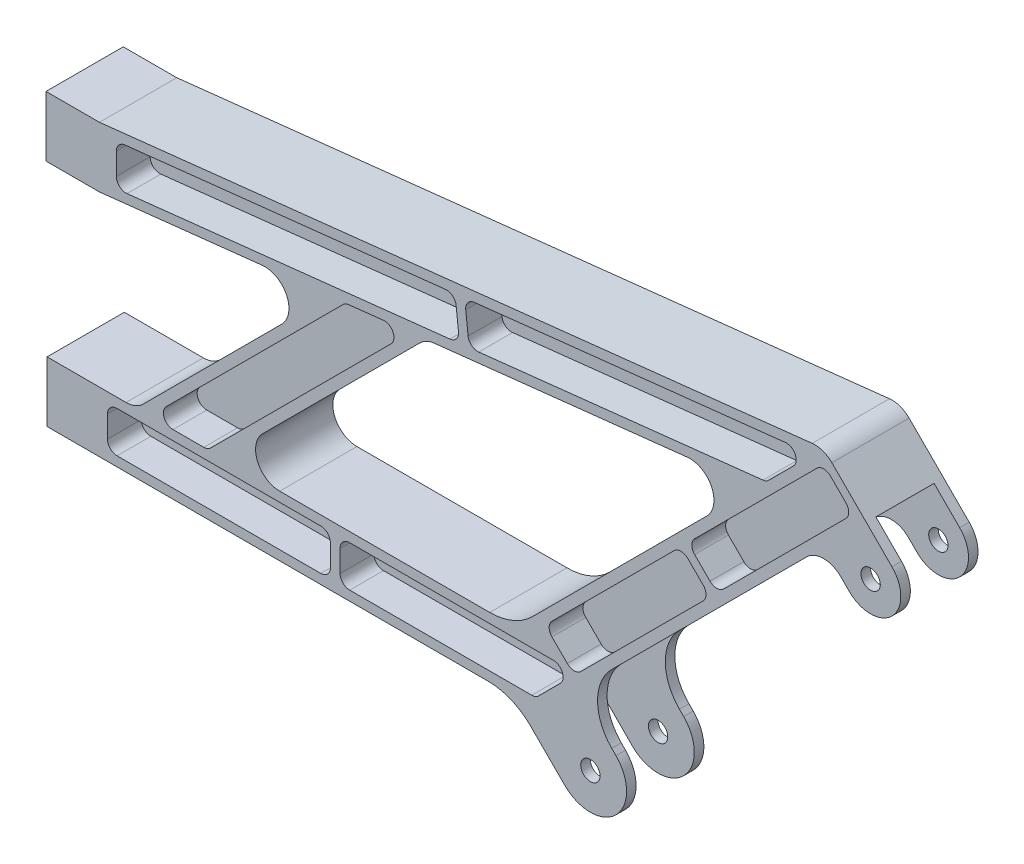
SolidWorks part; units mm, degrees
material "6061-T6 (SS)"
ref_plane "Front Plane" through (0, 0, 0) normal (0, 0, 1) x (1, 0, 0)
ref_plane "Top Plane" through (0, 0, 0) normal (0, 1, 0) x (1, 0, 0)
ref_plane "Right Plane" through (0, 0, 0) normal (1, 0, 0) x (0, 0, -1)
sketch "Sketch1" plane through (0, 0, 0) normal (0, 0, 1) x (1, 0, 0)
  line L1 (-157.7639, -90.8401) -> (-244.7728, -90.8401)
  line L2 (-67.8181, -11.2496) -> (-140.0863, -83.5177)
  line L3 (-16.0497, 33.7315) -> (8.8396, 8.8381)
  line L4 (-12.3744, -5.3033) -> (-8.8388, -8.8388)
  line L5 (-26.5165, -5.3033) -> (-107.2487, -86.0355)
  line L6 (-140.8326, -123.1624) -> (-126.6942, -137.3008)
  line L7 (-158.5102, -115.8401) -> (-341.1373, -115.8401)
  line L8 (-341.1373, -115.8401) -> (-341.1373, -90.8401)
  line L9 (-308.4124, -90.8401) -> (-341.1373, -90.8401)
  line L11 (-341.5776, -20.8403) -> (-319.4176, -20.8403)
  line L12 (-341.5776, -20.8403) -> (-341.5776, 4.1597)
  line L13 (-341.5776, 4.1597) -> (-319.4176, 4.1597)
  line L14 (-107.2487, -114.3198) -> (-105.481, -116.0876)
  line L15 (-319.4176, 4.1597) -> (-24.2138, 36.6012)
  line L17 (-301.3413, -87.9111) -> (-243.8773, -30.4471)
  line L18 (-75.9816, 5.7616) -> (-180.7131, -5.7479)
  line L19 (-251.8438, -73.769) -> (-186.6918, -8.6169)
  line L20 (-252.0407, -13.4359) -> (-319.4176, -20.8403)
  arc A4 (8.8388, -8.8388) -> (8.8396, 8.8381) centre (0, 0) ccw
  arc A5 (-8.8388, -8.8388) -> (8.8388, -8.8388) centre (0, 0) ccw
  arc A6 (-12.3744, -5.3033) -> (-26.5165, -5.3033) centre (-19.4454, -12.3744) ccw
  arc A7 (-107.2487, -86.0355) -> (-107.2487, -114.3198) centre (-93.1066, -100.1777) ccw
  arc A8 (-105.481, -137.3008) -> (-105.481, -116.0876) centre (-116.0876, -126.6942) ccw
  arc A9 (-126.6942, -137.3008) -> (-105.481, -137.3008) centre (-116.0876, -126.6942) ccw
  circle A12 centre (-116.0876, -126.6942) radius 4
  circle A13 centre (0, 0) radius 4
  arc A15 (-158.5102, -115.8401) -> (-140.8326, -123.1624) centre (-158.5102, -140.8401) cw
  arc A16 (-157.7639, -90.8401) -> (-140.0863, -83.5177) centre (-157.7639, -65.8401) ccw
  arc A20 (-67.8181, -11.2496) -> (-75.9816, 5.7616) centre (-74.8892, -4.1785) ccw
  arc A21 (-16.0497, 33.7315) -> (-24.2138, 36.6012) centre (-23.1214, 26.661) ccw
  arc A22 (-186.6918, -8.6169) -> (-180.7131, -5.7479) centre (-179.6207, -15.688) cw
  arc A23 (-244.7728, -90.8401) -> (-251.8438, -73.769) centre (-244.7728, -80.8401) cw
  arc A25 (-308.4124, -90.8401) -> (-301.3413, -87.9111) centre (-308.4124, -80.8401) ccw
  arc A26 (-252.0407, -13.4359) -> (-243.8773, -30.4471) centre (-250.9484, -23.3761) cw
  point P38 (0, 0)
  point P50 (-318.5667, -20.8403)
  dimension "D2" = 25
  dimension "D3" = 25
  dimension "D7" = 10
  dimension "D9" = 22.16
  dimension "D6" = 25
  dimension "D1" = 25
  dimension "D4" = 25
  dimension "D5" = 25
  dimension "D8" = 119.9998
extrude "Boss-Extrude1" add sketch "Sketch1" along normal blind 32
sketch "Sketch2" plane through (0, 0, 32) normal (0, 0, 1) x (1, 0, 0)
  line L0 (-107.2487, -86.0355) -> (-26.5165, -5.3033) construction
  line L1 (-137.5386, -110.6685) -> (-128.5386, -101.6685)
  line L2 (-131.367, -94.8401) -> (-215.77, -94.8401)
  line L3 (-67.8181, -11.2496) -> (-140.0863, -83.5177) construction
  line L4 (-107.2487, -86.0355) -> (-26.5165, -5.3033)
  line L5 (-67.8181, -11.2496) -> (-140.0863, -83.5177)
  line L6 (-22.272, 28.6397) -> (-72.893, -21.9813)
  line L7 (-119.9767, -93.1066) -> (-69.3575, -42.4874)
  line L8 (-131.9975, -86.7426) -> (-125.6335, -93.1066)
  line L9 (-10.2515, 22.275) -> (-16.6149, 28.6394)
  line L10 (-64.9897, -14.078) -> (-137.2579, -86.3462) construction
  line L11 (-110.0772, -83.2071) -> (-29.3449, -2.4749) construction
  line L12 (-341.1373, -115.8401) -> (-158.5102, -115.8401) construction
  line L13 (-341.1373, -115.8401) -> (-158.5102, -115.8401)
  line L14 (-312.1373, -111.8401) -> (-227.77, -111.8401)
  line L15 (-341.1373, -111.8401) -> (-158.5102, -111.8401) construction
  line L16 (-341.1373, -90.8401) -> (-341.1373, -115.8401) construction
  line L17 (-316.1373, -98.8401) -> (-316.1373, -107.8401)
  line L18 (-157.7639, -90.8401) -> (-244.7728, -90.8401) construction
  line L19 (8.8396, 8.8381) -> (-16.0497, 33.7315) construction
  line L20 (-140.8326, -123.1624) -> (-126.6942, -137.3008) construction
  line L21 (-65.1149, -38.2448) -> (-77.1357, -26.224) construction
  line L22 (-72.893, -27.6382) -> (-66.5291, -34.0022)
  line L23 (-75.7215, -30.4666) -> (-69.3575, -36.8306)
  line L24 (-81.3783, -30.4666) -> (-131.9975, -81.0858)
  line L25 (-60.8722, -34.0022) -> (-10.2517, 16.6183)
  line L26 (-221.77, -94.8401) -> (-221.77, -111.8401) construction
  line L27 (-219.77, -98.8401) -> (-219.77, -107.8401)
  line L28 (-223.77, -98.8401) -> (-223.77, -107.8401)
  line L29 (-215.77, -111.8401) -> (-140.367, -111.8401)
  line L30 (-227.77, -94.8401) -> (-312.1373, -94.8401)
  line L38 (-308.8907, 1.2925) -> (-176.1091, 15.8845)
  line L39 (-24.2138, 36.6012) -> (-319.4176, 4.1597) construction
  line L40 (-308.0168, -15.7138) -> (-174.2521, -1.0137)
  line L41 (-75.9816, 5.7616) -> (-180.7131, -5.7479) construction
  line L42 (-312.4538, -2.6836) -> (-312.4538, -11.7378)
  line L43 (-32.0118, 24.5568) -> (-42.1838, 14.3847)
  line L44 (-170.145, 16.5399) -> (-168.288, -0.3583) construction
  line L45 (-171.6961, 12.3454) -> (-170.713, 3.3993)
  line L46 (-167.7201, 12.7824) -> (-166.7369, 3.8362)
  line L47 (-164.181, 17.1954) -> (-35.2771, 31.3613)
  line L48 (-162.3239, 0.2971) -> (-44.5753, 13.2371)
  line L49 (-218.5658, -10.7925) -> (-291.7849, -84.0116)
  line L50 (-243.8773, -30.4471) -> (-301.3413, -87.9111) construction
  line L51 (-198.6096, -14.8779) -> (-273.4002, -89.6685)
  line L52 (-186.6918, -8.6169) -> (-251.8438, -73.769) construction
  line L53 (-216.1743, -9.6449) -> (-201.875, -8.0734)
  line L54 (-288.9565, -90.8401) -> (-276.2286, -90.8401)
  line L55 (-341.5776, 4.1597) -> (-341.5776, -20.8403) construction
  arc A0 (-22.272, 28.6397) -> (-16.6149, 28.6394) centre (-19.4436, 25.8113) cw
  arc A1 (-10.2517, 16.6183) -> (-10.2515, 22.275) centre (-13.0801, 19.4468) ccw
  arc A2 (-119.9767, -93.1066) -> (-125.6335, -93.1066) centre (-122.8051, -90.2782) cw
  arc A3 (-131.9975, -81.0858) -> (-131.9975, -86.7426) centre (-129.169, -83.9142) ccw
  arc A4 (-312.1373, -111.8401) -> (-316.1373, -107.8401) centre (-312.1373, -107.8401) cw
  arc A5 (-312.1373, -94.8401) -> (-316.1373, -98.8401) centre (-312.1373, -98.8401) ccw
  arc A6 (-140.367, -111.8401) -> (-137.5386, -110.6685) centre (-140.367, -107.8401) ccw
  arc A7 (-128.5386, -101.6685) -> (-131.367, -94.8401) centre (-131.367, -98.8401) ccw
  arc A8 (-75.7215, -30.4666) -> (-81.3783, -30.4666) centre (-78.5499, -33.295) ccw
  arc A9 (-69.3575, -36.8306) -> (-69.3575, -42.4874) centre (-72.1859, -39.659) cw
  arc A10 (-66.5291, -34.0022) -> (-60.8722, -34.0022) centre (-63.7006, -31.1737) ccw
  arc A11 (-72.893, -27.6382) -> (-72.893, -21.9813) centre (-70.0646, -24.8098) cw
  arc A12 (-223.77, -107.8401) -> (-227.77, -111.8401) centre (-227.77, -107.8401) cw
  arc A13 (-219.77, -107.8401) -> (-215.77, -111.8401) centre (-215.77, -107.8401) ccw
  arc A14 (-219.77, -98.8401) -> (-215.77, -94.8401) centre (-215.77, -98.8401) cw
  arc A15 (-223.77, -98.8401) -> (-227.77, -94.8401) centre (-227.77, -98.8401) ccw
  arc A20 (-44.5753, 13.2371) -> (-42.1838, 14.3847) centre (-45.0122, 17.2132) ccw
  arc A21 (-35.2771, 31.3613) -> (-32.0118, 24.5568) centre (-34.8402, 27.3852) cw
  arc A22 (-166.7369, 3.8362) -> (-162.3239, 0.2971) centre (-162.7609, 4.2732) ccw
  arc A23 (-167.7201, 12.7824) -> (-164.181, 17.1954) centre (-163.744, 13.2193) cw
  arc A24 (-170.713, 3.3993) -> (-174.2521, -1.0137) centre (-174.6891, 2.9623) cw
  arc A25 (-171.6961, 12.3454) -> (-176.1091, 15.8845) centre (-175.6722, 11.9085) ccw
  arc A26 (-308.0168, -15.7138) -> (-312.4538, -11.7378) centre (-308.4538, -11.7378) cw
  arc A27 (-308.8907, 1.2925) -> (-312.4538, -2.6836) centre (-308.4538, -2.6836) ccw
  arc A28 (-198.6096, -14.8779) -> (-201.875, -8.0734) centre (-201.438, -12.0495) ccw
  arc A29 (-218.5658, -10.7925) -> (-216.1743, -9.6449) centre (-215.7374, -13.6209) cw
  arc A30 (-273.4002, -89.6685) -> (-276.2286, -90.8401) centre (-276.2286, -86.8401) cw
  arc A31 (-288.9565, -90.8401) -> (-291.7849, -84.0116) centre (-288.9565, -86.8401) cw
  point P34 (-316.1373, -111.8401)
  point P53 (-78.5499, -27.6382)
  point P58 (-63.7006, -36.8306)
  point P69 (-223.77, -111.8401)
  point P72 (-219.77, -111.8401)
  point P75 (-219.77, -94.8401)
  point P78 (-223.77, -94.8401)
  point P117 (-166.3, -0.1398)
  point P120 (-168.157, 16.7584)
  point P123 (-170.276, -0.5768)
  point P126 (-172.1331, 16.3215)
  dimension "D2" = 4
  dimension "D6" = 4
  dimension "D11" = 4
  dimension "D13" = 4
  dimension "D16" = 4
  dimension "D22" = 4
  dimension "D19" = 4
  dimension "D4" = 25
  dimension "D5" = 4
  dimension "D7" = 4
  dimension "D8" = 4
  dimension "D9" = 32
  dimension "D10" = 2
  dimension "D12" = 2
  dimension "D14" = 4
  dimension "D15" = 4
  dimension "D17" = 4
  dimension "D18" = 4
  dimension "D20" = 4
  dimension "D21" = 2
  dimension "D23" = 4
  dimension "D1" = 4
  dimension "D3" = 4
extrude "Cut-Extrude1" cut sketch "Sketch2" against normal blind 14 contours L38 A27 L42 A26 L40 A24 L45 A25 | A23 L46 A22 L48 A20 L43 A21 L47 | A31 L54 A30 L51 A28 L53 A29 L49 | A11 L22 A10 L25 A1 L9 A0 L6 | A9 L23 A8 L24 A3 L8 A2 L7 | A14 L27 A13 L29 A6 L1 A7 L2 | L28 A15 L30 A5 L17 A4 L14 A12 region at (-175.3079, -103.1533, 32) region at (-41.5723, -2.6814, 32) region at (-100.6775, -61.7866, 32) region at (-269.9537, -103.3401, 32) region at (-241.8227, 0.0982, 32) region at (-100.9045, 15.7508, 32) region at (-245.4094, -49.7028, 32)
ref_plane "Plane1" through (0, 0, 16) normal (0, 0, 1) x (1, 0, 0)
mirror "Mirror1" about plane through (0, 0, 16) normal (0, 0, 1) of "Cut-Extrude1"
sketch "Sketch3" plane through (0, 0, 16) normal (0, 0, 1) x (1, 0, 0)
  line L0 (-158.5102, -115.8401) -> (-141.1954, -115.8401)
  line L1 (-98.969, -77.7558) -> (-134.1243, -112.9111)
  line L2 (-107.2487, -86.0355) -> (-26.5165, -5.3033) construction
  line L3 (-158.5102, -115.8401) -> (-116.5971, -149.2186)
  line L4 (-116.5971, -149.2186) -> (-66.3597, -110.0186)
  line L5 (-66.3597, -110.0186) -> (-98.969, -77.7558)
  line L6 (-29.0156, -7.8024) -> (7.8698, 29.083)
  line L7 (7.8698, 29.083) -> (26.3533, -15.3879)
  line L8 (26.3533, -15.3879) -> (-12.041, -17.819)
  line L9 (-12.041, -17.819) -> (-29.0156, -7.8024)
  arc A0 (-134.1243, -112.9111) -> (-141.1954, -115.8401) centre (-141.1954, -105.8401) cw
  dimension "D1" = 10
extrude "Cut-Extrude2" cut sketch "Sketch3" against normal blind 12.0515 and the other way blind 12.0515
sketch "Sketch5" plane through (0, 0, 16) normal (0, 0, 1) x (1, 0, 0)
  line L0 (0, -24.7236) -> (0, -90.9031)
